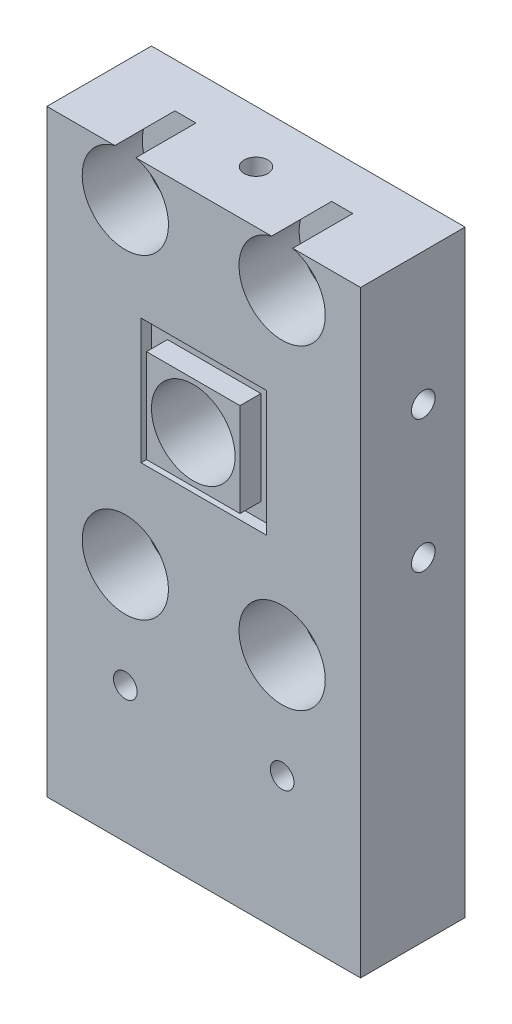
SolidWorks part; units mm, degrees
ref_plane "Front Plane" through (0, 0, 0) normal (0, 0, 1) x (1, 0, 0)
ref_plane "Top Plane" through (0, 0, 0) normal (0, 1, 0) x (1, 0, 0)
ref_plane "Right Plane" through (0, 0, 0) normal (1, 0, 0) x (0, 0, -1)
sketch "Sketch1" plane through (0, 0, 0) normal (0, 0, 1) x (1, 0, 0)
  line L1 (-15, 19.0246) -> (15, 19.0246)
  line L2 (-15, 19.0246) -> (-15, -38.1754)
  line L3 (-15, -38.1754) -> (15, -38.1754)
  line L4 (15, 19.0246) -> (15, -38.1754)
  line L5 (-4.4704, 4.4704) -> (4.4704, 4.4704)
  line L6 (-4.4704, 4.4704) -> (-4.4704, -4.4704)
  line L7 (-4.4704, -4.4704) -> (4.4704, -4.4704)
  line L8 (4.4704, 4.4704) -> (4.4704, -4.4704)
  line L9 (-5.9944, 5.9944) -> (5.9944, 5.9944)
  line L10 (-5.9944, 5.9944) -> (-5.9944, -5.9944)
  line L11 (-5.9944, -5.9944) -> (5.9944, -5.9944)
  line L12 (5.9944, 5.9944) -> (5.9944, -5.9944)
  circle A0 centre (0, 0) radius 4
  point P5 (7.5, -25.1754)
  point P13 (0, 5.9944)
  point P14 (0, 4.4704)
  point P15 (5.9944, 0)
  point P16 (4.4704, 0)
  point P17 (0, 19.0246)
  point P18 (-7.5, -25.1754)
  point P22 (7.5, -15.1754)
  point P23 (-7.5, -15.1754)
  point P24 (-7.5, 15.0246)
  point P25 (7.5, 15.0246)
  dimension "D6" = 8
  dimension "D1" = 30
  dimension "D2" = 57.2
  dimension "D3" = 8.9408
  dimension "D5" = 11.9888
  dimension "D4" = 13.0302
  dimension "D7" = 10
  dimension "D8" = 13
  dimension "D9" = 15
  dimension "D10" = 7.5
  dimension "D11" = 4
extrude "Boss-Extrude1" add sketch "Sketch1" along normal blind 10 contours L4 L1 L2 L3 L9 L12 L11 L10 region at (0, -10.4507, 0)
extrude "Boss-Extrude2" add sketch "Sketch1<7>" along normal blind 9 contours L12 L9 L10 L11 L5 L8 L7 L6 region at (0, 5.8249, 0)
sketch "Sketch1<7>" plane through (0, 0, 0) normal (0, 0, 1) x (1, 0, 0) same geometry as "Sketch1"
extrude "Boss-Extrude3" add sketch "Sketch1<8>" along normal blind 11 contours L8 L5 L6 L7 A0 region at (0, 4.344, 0)
sketch "Sketch1<8>" plane through (0, 0, 0) normal (0, 0, 1) x (1, 0, 0) same geometry as "Sketch1"
hole_wizard "#4-40 Tapped Hole1" positions "3DSketch1" profile "Sketch2" tap size "#4-40" standard "ANSI Inch" end condition through all
sketch3d "3DSketch1"
  point P0 (-7.5, 15.0246, 10)
  point P2 (7.5, 15.0246, 10)
  point P4 (-7.5, -15.1754, 10)
  point P6 (-7.5, -25.1754, 10)
  point P8 (7.5, -15.1754, 10)
  point P10 (7.5, -25.1754, 10)
sketch "Sketch2" plane through (-7.5, 15.0246, 10) normal (1, 0, 0) x (0, -1, 0)
  line L0 (0, 0) -> (0, 10)
  line L1 (0, 10) -> (1.1303, 10)
  line L2 (1.1303, 10) -> (1.1303, 0)
  line L5 (1.1303, 0) -> (0, 0)
  line L11 (0, -6.35) -> (0, 107.95) construction
  dimension "Thru Tap Drill Dia." = 2.2606
  dimension "Thru Tap Drill Depth" = 10
cosmetic thread "Hole Thread1" parameters "D2"=2.8448
cosmetic thread "Hole Thread2" parameters "D2"=2.8448
cosmetic thread "Hole Thread3" parameters "D2"=2.8448
cosmetic thread "Hole Thread4" parameters "D2"=2.8448
cosmetic thread "Hole Thread5" parameters "D2"=2.8448
cosmetic thread "Hole Thread6" parameters "D2"=2.8448
sketch "Sketch3" plane through (0, 0, 0) normal (0, 0, 1) x (1, 0, 0)
  line L0 (7.5, -11.5092) -> (10.675, -13.3423)
  line L1 (10.675, -13.3423) -> (10.675, -17.0085)
  line L2 (10.675, -17.0085) -> (7.5, -18.8416)
  line L3 (7.5, -18.8416) -> (4.325, -17.0085)
  line L4 (4.325, -17.0085) -> (4.325, -13.3423)
  line L5 (4.325, -13.3423) -> (7.5, -11.5092)
  circle A0 centre (7.5, -15.1754) radius 4.125
  circle A1 centre (-7.5, -15.1754) radius 4.125
  circle A4 centre (-7.5, 15.0246) radius 4.125
  circle A5 centre (7.5, 15.0246) radius 4.125
  point P16 (10.675, -15.1754)
  dimension "D4" = 8.25
  dimension "D1" = 6.35
  dimension "D2" = 6.35
  dimension "D3" = 7.3323
extrude "Cut-Extrude1" cut sketch "Sketch3" against normal blind 5.75 from surface contours L5 L4 L3 L2 L1 L0 | A0 L4 L5 L0 L1 L2 L3 | A5 | A4 | A1 region at (7.5, -15.1754, 0) region at (3.4917, -15.1754, 0) region at (-7.5, -15.1754, 0) region at (-7.5, 15.0246, 0) region at (7.5, 15.0246, 0) starting at face at (-6.3697, 15.0246, 10)
hole_wizard "#4-40 Tapped Hole2" positions "3DSketch2" profile "Sketch4" tap size "#4-40" standard "ANSI Inch"
sketch3d "3DSketch2"
  line L0 (15, -38.1754, 10) -> (15, -38.1754, 0) construction
  line L1 (-15, -38.1754, 10) -> (-15, -38.1754, 0) construction
  line L4 (-15, -38.1754, 0) -> (15, -38.1754, 0) construction
  line L5 (-15, 19.0246, 0) -> (15, 19.0246, 0) construction
  line L6 (-15, 19.0246, 10) -> (-15, 19.0246, 0) construction
  line L7 (15, 19.0246, 10) -> (15, -38.1754, 10) construction
  line L8 (15, 19.0246, 10) -> (15, 19.0246, 0) construction
  point P0 (9, -38.1754, 5)
  point P2 (-9, -38.1754, 5)
  point P4 (-5, -38.1754, 5)
  point P6 (5, -38.1754, 5)
  point P8 (0, 19.0246, 5)
  point P30 (0, 19.0246, 5)
  point P44 (15, 6.3546, 4)
  point P46 (-15, 6.3546, 4)
  point P58 (15, -6.3454, 4)
  point P60 (-15, -6.3454, 4)
  dimension "D10" = 12.67
  dimension "D1" = 6
  dimension "D2" = 4
  dimension "D3" = 4
  dimension "D4" = 6
  dimension "D5" = 5
  dimension "D6" = 5
  dimension "D7" = 15
  dimension "D8" = 6
  dimension "D9" = 12.7
cosmetic thread "Hole Thread7"
cosmetic thread "Hole Thread8"
cosmetic thread "Hole Thread9"
cosmetic thread "Hole Thread10"
cosmetic thread "Hole Thread14"
cosmetic thread "Hole Thread15"
cosmetic thread "Hole Thread16"
cosmetic thread "Hole Thread17"
cosmetic thread "Hole Thread18"
sketch "Sketch4" plane through (9, -38.1754, 5) normal (1, 0, 0) x (0, 0, -1)
  line L0 (0, 0) -> (0, 8.2692)
  line L1 (0, 8.2692) -> (1.1303, 7.59)
  line L2 (1.1303, 7.59) -> (1.1303, 0)
  line L5 (1.1303, 0) -> (0, 0)
  line L10 (0, 8.2692) -> (-1.1303, 7.59) construction
  line L11 (0, -6.35) -> (0, 107.95) construction
  dimension "Tap Drill Dia." = 2.2606
  dimension "Tap Drill Depth" = 7.59
  dimension "Drill Angle" = 118
cosmetic thread "Hole Thread19"
equation "\"D10@Sketch1\"=(\"D1@Sketch1\"-\"D9@Sketch1\")/2"
equation "\"D10@3DSketch2\"=(19.02-(12.7/2))"
